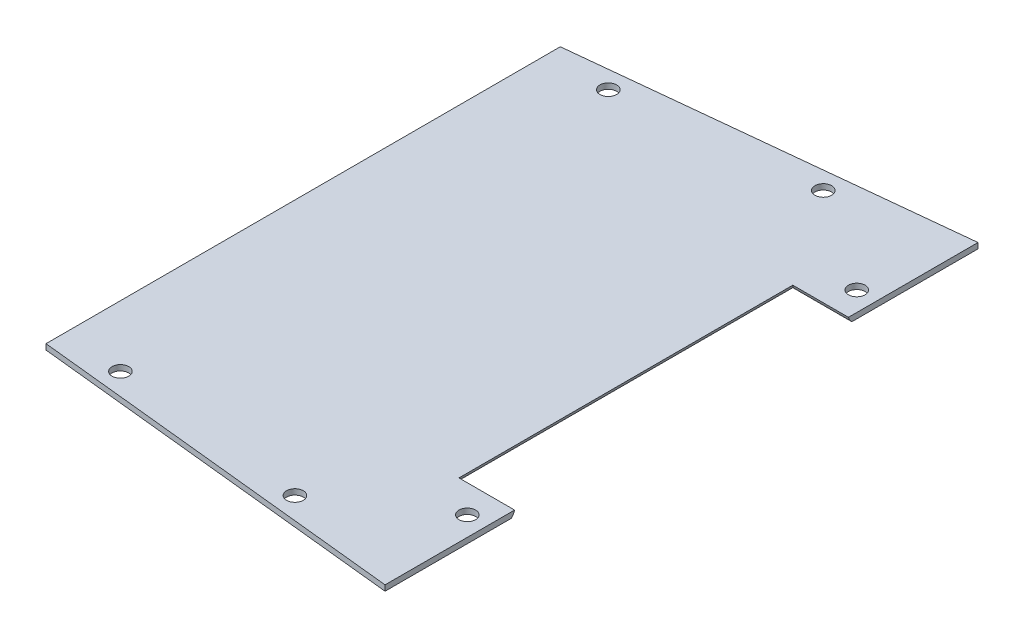
SolidWorks part; units mm, degrees
ref_plane "정면" through (0, 0, 0) normal (0, 0, 1) x (1, 0, 0)
ref_plane "윗면" through (0, 0, 0) normal (0, 1, 0) x (1, 0, 0)
ref_plane "우측면" through (0, 0, 0) normal (1, 0, 0) x (0, 0, -1)
sketch "스케치2" plane through (0, 0, 0) normal (0, 1, 0) x (1, 0, 0)
  line L0 (34, 30) -> (34, 53.2813)
  line L1 (34, 53.2813) -> (-34, 46.212)
  line L2 (34, -53.2813) -> (-34, -46.212)
  line L3 (34, -30) -> (34, -53.2813)
  line L12 (-34, 46.212) -> (-34, -46.212)
  line L13 (34, 30) -> (24, 30)
  line L14 (24, 30) -> (24, -30)
  line L15 (24, -30) -> (34, -30)
  point P1 (-34, 0)
  point P2 (0, 49.7466)
  dimension "D1" = 84.065
  dimension "D2" = 84.065
  dimension "D3" = 95.935
  dimension "D4" = 95.935
  dimension "D5" = 92.424
  dimension "D6" = 106.5626
  dimension "D7" = 68
  dimension "D8" = 60
  dimension "D9" = 58
extrude "보스-돌출1" add sketch "스케치2" along normal blind 1
sketch "스케치3" plane through (0, 0, 0) normal (0, -1, 0) x (1, 0, 0)
  line L28 (12, 47.4753) -> (12, -47.4753) construction
  line L29 (-23, 43.8367) -> (-23, -43.8367) construction
  line L30 (34, 53.2813) -> (34, 30) construction
  line L33 (-30.5, -43.057) -> (-30.5, 43.057)
  line L34 (30.5, -30) -> (30.5, -49.3986)
  line L35 (30.5, -49.3986) -> (-30.5, -43.057)
  line L36 (30.5, 49.3986) -> (30.5, 30)
  line L37 (-30.5, 43.057) -> (30.5, 49.3986)
  line L38 (-30.5, -43.057) -> (-30.5, 43.057) construction
  line L39 (30.5, -30) -> (30.5, -49.3986) construction
  line L40 (30.5, -49.3986) -> (-30.5, -43.057) construction
  line L41 (30.5, 49.3986) -> (30.5, 30) construction
  line L42 (-30.5, 43.057) -> (30.5, 49.3986) construction
  circle A0 centre (-23, 43.8367) radius 1.5
  circle A1 centre (12, 47.4753) radius 1.5
  circle A2 centre (30.5, 35) radius 1.5
  circle A3 centre (30.5, -35) radius 1.5
  circle A4 centre (-23, -43.8367) radius 1.5
  circle A5 centre (12, -47.4753) radius 1.5
  dimension "D2" = 3
  dimension "D3" = 70
  dimension "D4" = 35
  dimension "D5" = 35
  dimension "D6" = 22
  dimension "D1" = 3.5
extrude "컷-돌출1" cut sketch "스케치3" against normal up to next
sketch "스케치4" plane through (0, 0, 0) normal (0, -1, 0) x (1, 0, 0)
  line L4 (-34, 44.0001) -> (-34, -44.0001)
  line L5 (-34, -46.212) -> (-34, 46.212) construction
  line L15 (31.8, 30) -> (24, 30)
  line L16 (24, 30) -> (24, -30)
  line L17 (24, -30) -> (31.8, -30)
  line L18 (31.8, -37.75) -> (31.8, -50.8407)
  line L19 (9.1303, -48.484) -> (-20.3992, -45.4141)
  line L20 (31.8, -30) -> (31.8, -50.8407)
  line L21 (31.8, 50.8407) -> (31.8, 30)
  line L22 (31.8, -50.8407) -> (-31.8, -44.2288)
  line L23 (-31.8, -44.2288) -> (-31.8, 44.2288)
  line L24 (-31.8, 44.2288) -> (31.8, 50.8407)
  line L25 (31.8, -30) -> (31.8, -32.25)
  line L26 (31.8, 50.8407) -> (31.8, 37.75)
  line L27 (31.8, -50.8407) -> (14.6008, -49.0527)
  line L29 (-34, 44.0001) -> (-25.8697, 44.8454)
  line L30 (-25.8697, -44.8454) -> (-34, -44.0001)
  line L31 (-20.3992, 45.4141) -> (9.1303, 48.484)
  line L32 (14.6008, 49.0527) -> (31.8, 50.8407)
  line L33 (31.8, 32.25) -> (31.8, 30)
  line L34 (30.5, 37.75) -> (31.8, 37.75)
  line L35 (30.5, 32.25) -> (31.8, 32.25)
  line L36 (30.5, -32.25) -> (31.8, -32.25)
  line L37 (30.5, -37.75) -> (31.8, -37.75)
  line L38 (14.6008, -49.0527) -> (14.7353, -47.7597)
  line L39 (9.1303, -48.484) -> (9.2647, -47.191)
  line L40 (-25.8697, -44.8454) -> (-25.7353, -43.5523)
  line L41 (-20.3992, -45.4141) -> (-20.2647, -44.1211)
  line L42 (-20.3992, 45.4141) -> (-20.2647, 44.1211)
  line L43 (-25.8697, 44.8454) -> (-25.7353, 43.5523)
  line L44 (9.1303, 48.484) -> (9.2647, 47.191)
  line L45 (14.6008, 49.0527) -> (14.7353, 47.7597)
  arc A0 (-25.7353, 43.5523) -> (-20.2647, 44.1211) centre (-23, 43.8367) ccw
  arc A1 (9.2647, 47.191) -> (14.7353, 47.7597) centre (12, 47.4753) ccw
  arc A2 (30.5, 37.75) -> (30.5, 32.25) centre (30.5, 35) ccw
  arc A3 (30.5, -32.25) -> (30.5, -37.75) centre (30.5, -35) ccw
  arc A4 (14.7353, -47.7597) -> (9.2647, -47.191) centre (12, -47.4753) ccw
  arc A5 (-20.2647, -44.1211) -> (-25.7353, -43.5523) centre (-23, -43.8367) ccw
  dimension "D1" = 5.5
  dimension "D2" = 2.2
extrude "보스-돌출2" add sketch "스케치4" along normal blind 0.5
fillet "필렛1" radius 2 3 edges at (27.9, -0.5, -30) (27.9, -0.5, 30) (24, -0.5, 0)
